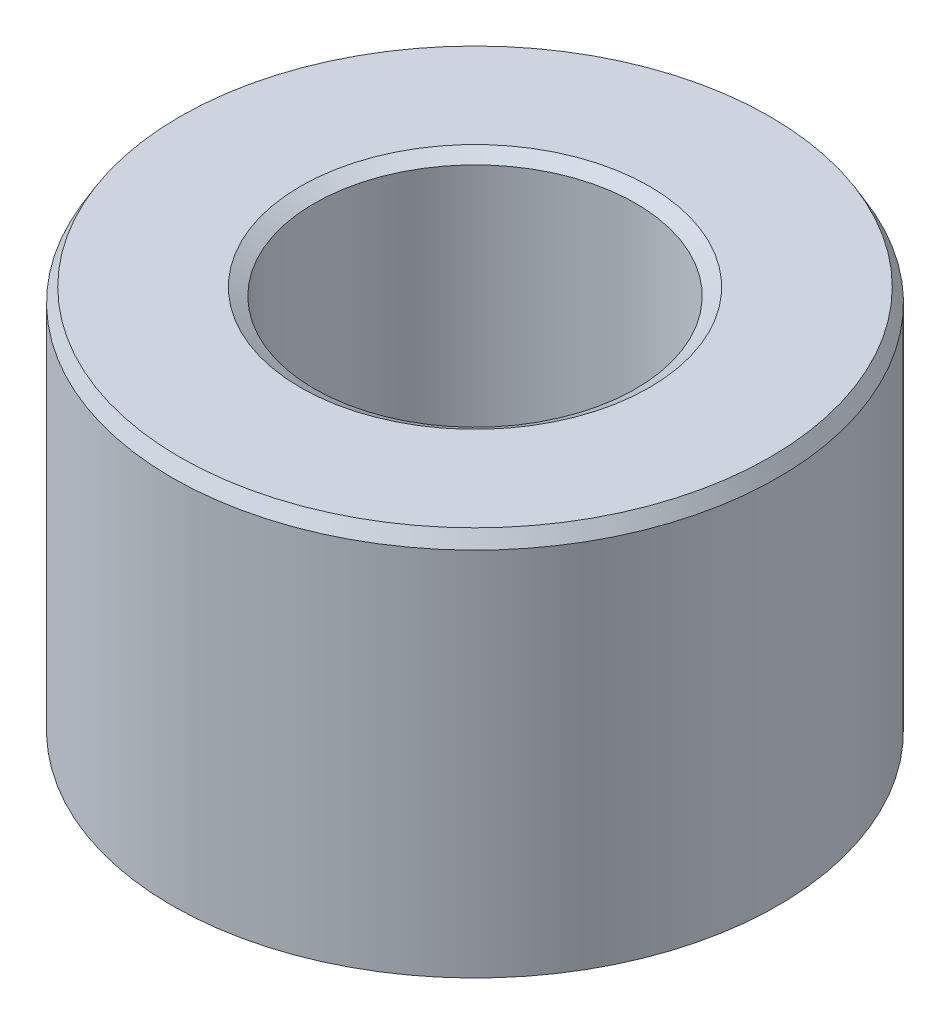
SolidWorks part; units mm, degrees
ref_plane "Front Plane" through (0, 0, 0) normal (0, 0, 1) x (1, 0, 0)
ref_plane "Top Plane" through (0, 0, 0) normal (0, 1, 0) x (1, 0, 0)
ref_plane "Right Plane" through (0, 0, 0) normal (1, 0, 0) x (0, 0, -1)
sketch "Sketch1" plane through (0, 0, 0) normal (0, 1, 0) x (1, 0, 0)
  circle A0 centre (0, 0) radius 7.5
  dimension "SLEEVE_OD" = 15
extrude "Boss-Extrude1" add sketch "Sketch1" along normal blind 9.7087
sketch "Sketch2" plane through (0, 0, 0) normal (0, 1, 0) x (1, 0, 0)
  circle A0 centre (0, 0) radius 3.9777
  dimension "BORE_D" = 7.9555
extrude "Cut-Extrude1" cut sketch "Sketch2" along normal through all
chamfer "Chamfer1" distance 0.34 angle 30 4 edges at (0, 9.7087, 3.9777) (0, 0, 3.9777) (0, 0, 7.5) (0, 9.7087, 7.5) first distance on face at (0, 9.7087, 3.9777) first distance on face at (0, 0, 3.9777) first distance on face at (0, 9.7087, 7.5)
